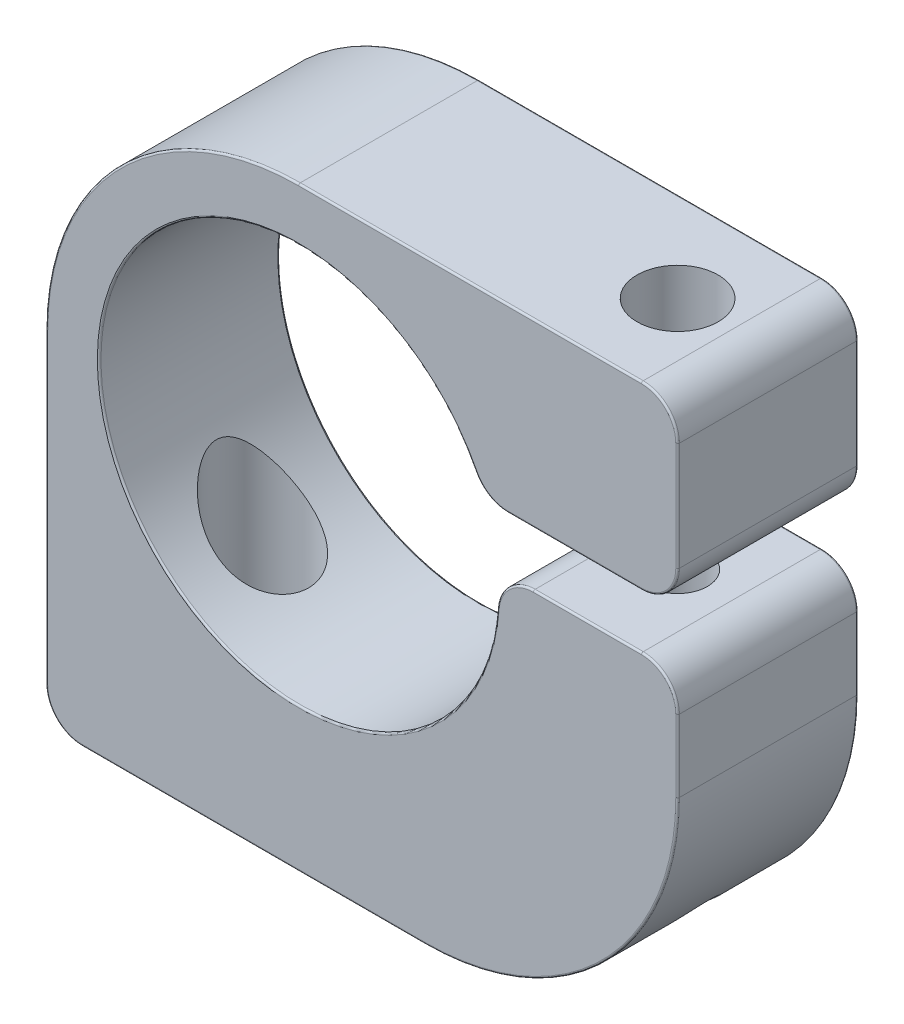
SolidWorks part; units mm, degrees
material "Сплав 2024"
ref_plane "Спереди" through (0, 0, 0) normal (0, 0, 1) x (1, 0, 0)
ref_plane "Сверху" through (0, 0, 0) normal (0, 1, 0) x (1, 0, 0)
ref_plane "Справа" through (0, 0, 0) normal (1, 0, 0) x (0, 0, -1)
sketch "Эскиз1" plane through (0, 0, 0) normal (0, 0, 1) x (1, 0, 0)
  line L0 (10.3006, 4) -> (21, 4)
  line L1 (0, 14) -> (21, 14)
  line L2 (-14, 0) -> (-14, -19)
  line L3 (-14, -19) -> (7, -19)
  line L4 (21, 14) -> (21, 4)
  line L5 (21, 1) -> (11.0047, 1)
  line L6 (21, 1) -> (21, -5)
  arc A0 (10.3006, 4) -> (11.0047, 1) centre (0, 0) ccw
  arc A1 (0, 14) -> (-14, 0) centre (0, 0) ccw
  arc A2 (7, -19) -> (21, -5) centre (7, -5) ccw
  dimension "D1" = 22.1
  dimension "D2" = 28
  dimension "D7" = 28
  dimension "D3" = 35
  dimension "D4" = 3
  dimension "D5" = 10
  dimension "D6" = 20
extrude "Бобышка-Вытянуть1" add sketch "Эскиз1" along normal blind 10
sketch "Эскиз2" plane through (0, 14, 0) normal (0, 1, 0) x (1, 0, 0)
  line L0 (21, -5) -> (1.7357, -5) construction
  line L1 (21, -10) -> (21, 0) construction
  line L2 (16, 0) -> (16, -10) construction
  line L3 (21, 0) -> (0, 0) construction
  line L4 (21, -10) -> (0, -10) construction
  dimension "D1" = 5
hole_wizard "Отверстие с зазором M41" positions "Эскиз4" profile "Эскиз3" hole size "M4" standard "Ansi Metric"
sketch "Эскиз4" plane through (0, 14, 0) normal (0, 1, 0) x (1, 0, 0)
  line L0 (16, 0) -> (16, -10) construction
  point P0 (16, -5)
sketch "Эскиз3" plane through (16, 14, 5) normal (1, 0, 0) x (0, 0, 1)
  line L0 (0, 0) -> (0, 5.3519)
  line L1 (0, 5.3519) -> (2.25, 4)
  line L2 (2.25, 4) -> (2.25, 0)
  line L5 (2.25, 0) -> (0, 0)
  line L10 (0, 5.3519) -> (-2.25, 4) construction
  line L11 (0, -6.35) -> (0, 107.95) construction
  dimension "Диаметр отверстия" = 4.5
  dimension "Глубина отверстия" = 4
  dimension "Угол заточки сверла" = 118
hole_wizard "Отверстие обработанное метчиком M4x0.71" positions "Эскиз6" profile "Эскиз5" tap size "M4x0.7" standard "Ansi Metric" end condition through all
sketch "Эскиз6" plane through (0, 1, 0) normal (0, 1, 0) x (1, 0, 0)
  line L0 (16, 0) -> (16, -10) construction
  point P0 (16, -5)
sketch "Эскиз5" plane through (16, 1, 5) normal (1, 0, 0) x (0, 0, 1)
  line L0 (0, 0) -> (0, 20)
  line L1 (0, 20) -> (1.65, 20)
  line L2 (1.65, 20) -> (1.65, 0)
  line L5 (1.65, 0) -> (0, 0)
  line L11 (0, -6.35) -> (0, 107.95) construction
  dimension "Диаметр проходного сверла" = 3.3
  dimension "Глубина проходного сверла" = 20
cosmetic thread "Отверстие резьбы1" parameters "D2"=4
sketch "Эскиз7" plane through (0, -19, 0) normal (0, -1, 0) x (1, 0, 0)
  line L0 (-14, 5) -> (0, 5) construction
  line L1 (-14, 10) -> (-14, 0) construction
  line L2 (-7, 10) -> (-7, 0) construction
  line L3 (-14, 10) -> (7, 10) construction
  line L4 (-14, 0) -> (7, 0) construction
  dimension "D1" = 7
hole_wizard "Отверстие обработанное метчиком 1/4-201" positions "Эскиз9" profile "Эскиз8" tap size "1/4-20" standard "Ansi Inch" end condition up to next
sketch "Эскиз9" plane through (0, -19, 0) normal (0, -1, 0) x (-1, 0, 0)
  line L0 (14, -5) -> (0, -5) construction
  point P0 (7, -5)
sketch "Эскиз8" plane through (-7, -19, 5) normal (1, 0, 0) x (0, 0, -1)
  line L0 (0, 0) -> (0, 10.45)
  line L1 (0, 10.45) -> (2.5527, 10.45)
  line L2 (2.5527, 10.45) -> (2.5527, 0)
  line L5 (2.5527, 0) -> (0, 0)
  line L11 (0, -6.35) -> (0, 107.95) construction
  dimension "Диаметр проходного сверла" = 5.1054
  dimension "Глубина проходного сверла" = 10.45
cosmetic thread "Отверстие резьбы2" parameters "D2"=6.35
fillet "Скругление1" radius 2 6 edges at (-14, -19, 5) (21, 14, 5) (21, 4, 5) (21, 1, 5) (11.0047, 1, 5) (10.3006, 4, 5)
fillet "Скругление2" radius 0.1 32 edges at (-9.8995, 9.8995, 10) (9.5, 14, 10) (20.4142, 13.4142, 10) (21, 9, 10) (20.4142, 4.5858, 10) (15.2944, 4, 10) (10.5494, 4.2913, 10) (-10.8286, -2.2009, 10) (11.6527, 0.4674, 10) (16.0058, 1, 10) (20.4142, 0.4142, 10) (21, -3, 10) (16.8995, -14.8995, 10) (-2.5, -19, 10) (-13.4142, -18.4142, 10) (-14, -8.5, 10) (16.8995, -14.8995, 0) (21, -3, 0) (20.4142, 0.4142, 0) (16.0058, 1, 0) (11.6527, 0.4674, 0) (-10.8286, -2.2009, 0) (10.5494, 4.2913, 0) (15.2944, 4, 0) (20.4142, 4.5858, 0) (21, 9, 0) (20.4142, 13.4142, 0) (9.5, 14, 0) (-9.8995, 9.8995, 0) (-14, -8.5, 0) (-13.4142, -18.4142, 0) (-2.5, -19, 0)
